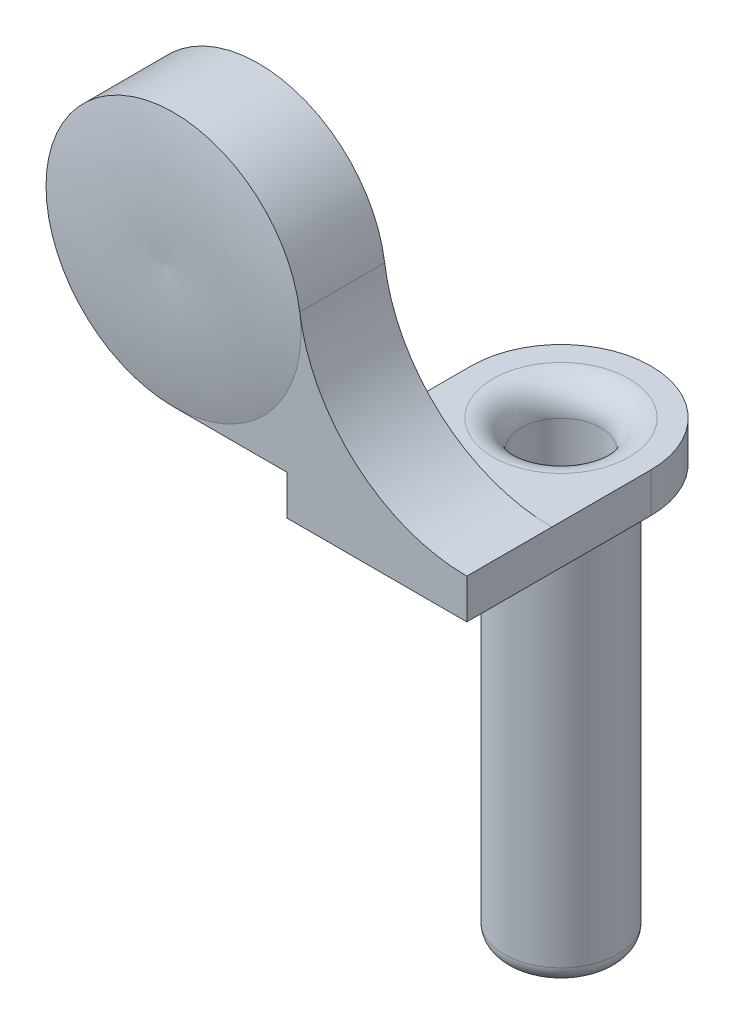
SolidWorks part; units mm, degrees
ref_plane "前视基准面" through (0, 0, 0) normal (0, 0, 1) x (1, 0, 0)
ref_plane "上视基准面" through (0, 0, 0) normal (0, 1, 0) x (1, 0, 0)
ref_plane "右视基准面" through (0, 0, 0) normal (1, 0, 0) x (0, 0, -1)
sketch "草图1" plane through (0, 0, 0) normal (0, 1, 0) x (1, 0, 0)
  line L0 (0, 0) -> (0, 4.3268) construction
  line L1 (0, 0) -> (6.0935, 0) construction
  circle A0 centre (0, 0) radius 2
  dimension "D1" = 4
extrude "凸台-拉伸1" add sketch "草图1" along normal blind 16
ref_plane "基准面2" through (0, 0, 3.5) normal (0, 0, 1) x (1, 0, 0)
sketch "草图2" plane through (0, 0, 3.5) normal (0, 0, 1) x (1, 0, 0)
  line L0 (-2, 19.9066) -> (-2, 24.8439) construction
  line L1 (-2, 16) -> (-2, 0) construction
  line L2 (-2.327, 16) -> (-3.6912, 16) construction
  line L3 (2, 16) -> (-2, 16) construction
  line L4 (3.175, 16) -> (-3.8901, 23.5703)
  line L5 (3.175, 16) -> (-7.18, 16)
  line L6 (0, 19.5869) -> (0, 22.2425) construction
  arc A0 (-3.8901, 23.5703) -> (-7.18, 16) centre (-7.18, 20.5) ccw
  dimension "D1" = 4.5
  dimension "D2" = 9
  dimension "D3" = 3.175
  dimension "D4" = 5.18
extrude "凸台-拉伸2" add sketch "草图2" along normal blind 3
sketch "草图4" plane through (0, 0, 3.5) normal (0, 0, -1) x (-1, 0, 0)
  circle A0 centre (7.18, 20.5) radius 3.15
  dimension "D1" = 6.3
extrude "切除-拉伸6" cut sketch "草图4" against normal blind 2.775
fillet "圆角3" radius 0.6 1 edges at (0, 0, 2)
sketch "草图7" plane through (0, 16, 0) normal (0, 1, 0) x (1, 0, 0)
  circle A0 centre (0, 0) radius 3.175
  dimension "D1" = 6.35
extrude "凸台-拉伸3" add sketch "草图7" against normal blind 1.4
sketch "草图10" plane through (0, 0, 0) normal (0, -1, 0) x (1, 0, 0)
  circle A1 centre (0, 0) radius 1.4
  dimension "D1" = 2.8
extrude "切除-拉伸9" cut sketch "草图10" against normal through all both and the other way through all
fillet "圆角6" radius 1 1 edges at (0, 16, 1.4)
ref_plane "基准面1" through (0, 20.5, 0) normal (0, -1, 0) x (-1, 0, 0)
sketch "草图12" plane through (0, 20.5, 0) normal (0, -1, 0) x (-1, 0, 0)
  line L0 (7.18, -6.5) -> (7.18, -6.8)
  line L2 (7.18, -6.5) -> (11.68, -6.5)
  arc A0 (11.68, -6.5) -> (7.18, -6.8) centre (8.3868, 8.9975) cw
  dimension "D1" = 0.3
  dimension "D2" = 4.5
revolve "旋转1" add sketch "草图12" angle 360 about L0
sketch "草图13" plane through (0, 0, 6.5) normal (0, 0, 1) x (1, 0, 0)
  line L0 (-3.175, 16) -> (-3.175, 14.6)
  line L1 (-3.175, 14.6) -> (3.175, 14.6)
  line L2 (3.175, 14.6) -> (3.175, 16)
  line L3 (3.175, 16) -> (-3.175, 16)
extrude "凸台-拉伸4" add sketch "草图13" against normal up to surface (6.5 mm away) up to face at (0, 14.6, 3.175)
sketch "草图14" plane through (0, 14.6, 0) normal (0, -1, 0) x (1, 0, 0)
  line L1 (3.175, 6.5) -> (3.175, 0)
  line L2 (3.175, 6.5) -> (3.175, 7.3402)
  line L3 (3.175, 7.3402) -> (0.175, 7.3402)
  arc A1 (0.175, 7.3402) -> (3.175, 0) centre (-9.9221, -1.0698) cw
  dimension "D1" = 3
extrude "切除-拉伸10" [suppressed] cut sketch "草图14" against normal through all
fillet "圆角8" radius 0.3 1 edges at (-10.33, 20.5, 3.5)
sketch "草图15" plane through (0, 0, 3.5) normal (0, 0, -1) x (-1, 0, 0)
  line L0 (3.175, 16) -> (3.175, 25.23) construction
  line L1 (-3.175, 16) -> (5.0764, 24.8414) construction
  line L2 (3.175, 16) -> (-3.175, 16) construction
  line L6 (3.8901, 23.5703) -> (-3.175, 16)
  arc A2 (-3.175, 16) -> (2.7239, 21.127) centre (-3.175, 21.957) ccw
  arc A3 (3.8901, 23.5703) -> (2.7239, 21.127) centre (7.18, 20.5) ccw
extrude "切除-拉伸12" cut sketch "草图15" against normal up to next
